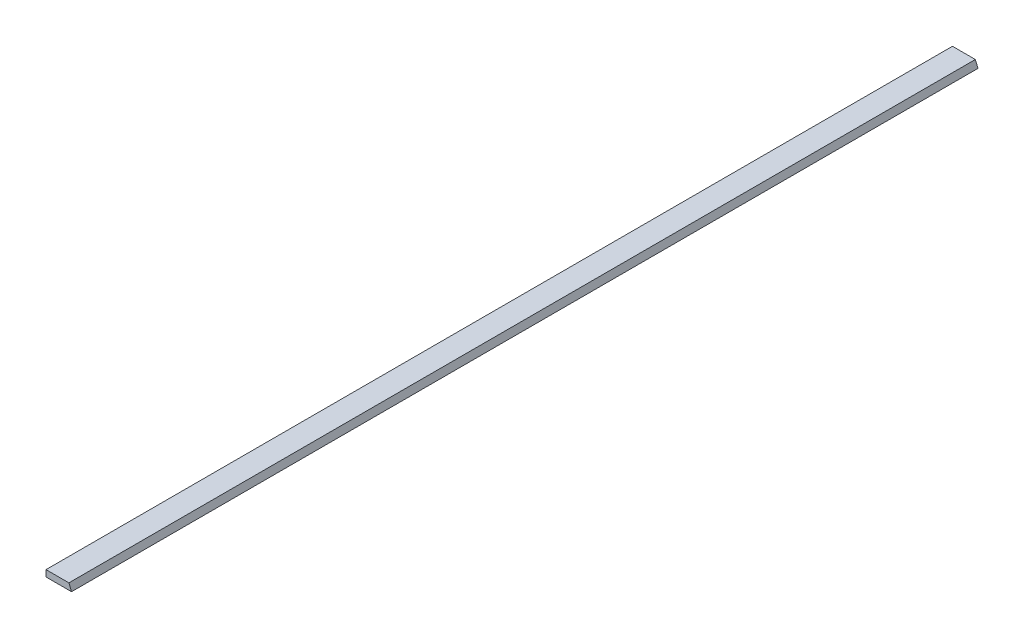
SolidWorks part; units mm, degrees
ref_plane "Front Plane" through (0, 0, 0) normal (0, 0, 1) x (1, 0, 0)
ref_plane "Top Plane" through (0, 0, 0) normal (0, 1, 0) x (1, 0, 0)
ref_plane "Right Plane" through (0, 0, 0) normal (1, 0, 0) x (0, 0, -1)
sketch "Sketch1" plane through (0, 0, 0) normal (0, 0, 1) x (1, 0, 0)
  line L0 (0, 0) -> (0, 6.35)
  line L1 (0, 6.35) -> (22.7697, 6.35)
  line L2 (22.7697, 6.35) -> (25.4, 0)
  line L3 (25.4, 0) -> (0, 0)
  dimension "D1" = 67.5
  dimension "D2" = 25.4
  dimension "D3" = 6.35
extrude "Boss-Extrude1" add sketch "Sketch1" along normal blind 901.7
